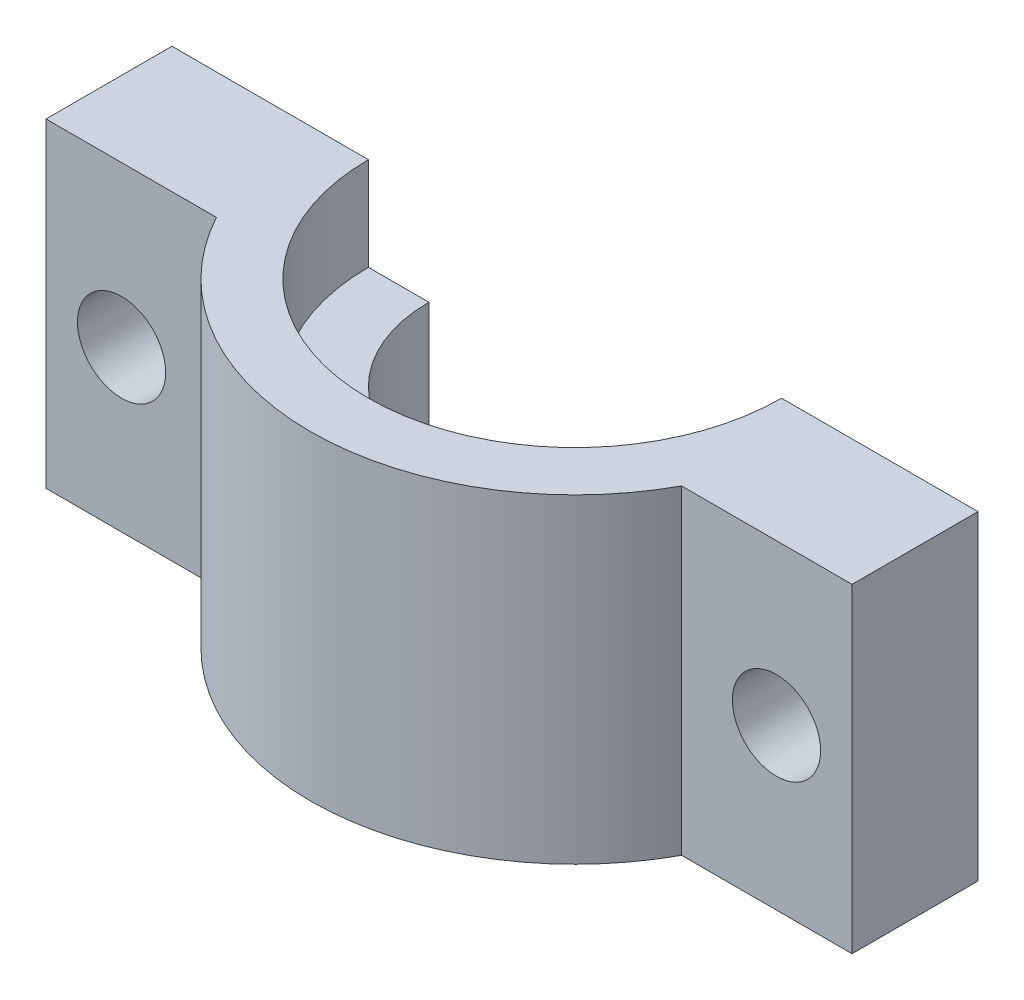
SolidWorks part; units mm, degrees
ref_plane "Front Plane" through (0, 0, 0) normal (0, 0, 1) x (1, 0, 0)
ref_plane "Top Plane" through (0, 0, 0) normal (0, 1, 0) x (1, 0, 0)
ref_plane "Right Plane" through (0, 0, 0) normal (1, 0, 0) x (0, 0, -1)
sketch "Sketch1" plane through (0, 0, 0) normal (0, 0, 1) x (1, 0, 0)
  line L1 (-16, 6.35) -> (16, 6.35)
  line L2 (-16, 6.35) -> (-16, -6.35)
  line L3 (-16, -6.35) -> (16, -6.35)
  line L4 (16, 6.35) -> (16, -6.35)
  line L5 (-16, 6.35) -> (16, -6.35) construction
  line L6 (-16, -6.35) -> (16, 6.35) construction
  point P0 (0, 0)
  dimension "D1" = 32
  dimension "D2" = 12.7
extrude "Boss-Extrude1" add sketch "Sketch1" along normal blind 12
sketch "Sketch3" plane through (0, 0, 0) normal (1, 0, 0) x (0, 0, -1)
  line L0 (0, 6.35) -> (-8.2, 6.35)
  line L1 (0, 6.35) -> (0, -6.35)
  line L2 (-12, 6.35) -> (0, 6.35) construction
  line L3 (-8.2, 6.35) -> (-8.2, 2.65)
  line L4 (-8.2, 2.65) -> (-5.8, 2.65)
  line L5 (-5.8, 2.65) -> (-5.8, -3.35)
  line L6 (-5.8, -3.35) -> (-8.2, -3.35)
  line L7 (-8.2, -3.35) -> (-8.2, -6.35)
  line L8 (-8.2, -6.35) -> (0, -6.35)
  line L9 (-12, -6.35) -> (0, -6.35) construction
  line L11 (0, -6.35) -> (0, 6.35) construction
  dimension "D1" = 8.2
  dimension "D2" = 5.8
  dimension "D3" = 3.7
  dimension "D4" = 3
revolve "Cut-Revolve1" cut sketch "Sketch3" angle 360 about L1
sketch "Sketch4" plane through (0, 6.35, 0) normal (0, 1, 0) x (1, 0, 0)
  line L0 (-16, -5) -> (-9.2331, -5)
  line L1 (-16, -12) -> (-16, 0) construction
  line L2 (9.2331, -5) -> (16, -5)
  line L3 (16, -12) -> (16, 0) construction
  line L7 (-16, -5) -> (-16, -15)
  line L8 (-16, -15) -> (16, -15)
  line L9 (16, -15) -> (16, -5)
  line L10 (-8.2, 0) -> (-16, 0) construction
  line L11 (16, -12) -> (-16, -12) construction
  arc A0 (-9.2331, -5) -> (9.2331, -5) centre (0, 0) ccw
  dimension "D1" = 21
  dimension "D2" = 5
  dimension "D3" = 3
extrude "Cut-Extrude1" cut sketch "Sketch4" against normal through all
sketch "Sketch5" plane through (0, 0, 5) normal (0, 0, 1) x (1, 0, 0)
  line L0 (-16, 0) -> (-10, 0) construction
  line L1 (-16, -6.35) -> (-16, 6.35) construction
  line L2 (16, 0) -> (10, 0) construction
  line L3 (16, -6.35) -> (16, 6.35) construction
  circle A0 centre (-13, 0) radius 1.75
  circle A1 centre (13, 0) radius 1.75
  dimension "D3" = 3.5
  dimension "D4" = 3.5
  dimension "D1" = 6
  dimension "D2" = 6
extrude "Cut-Extrude2" cut sketch "Sketch5" against normal through all
